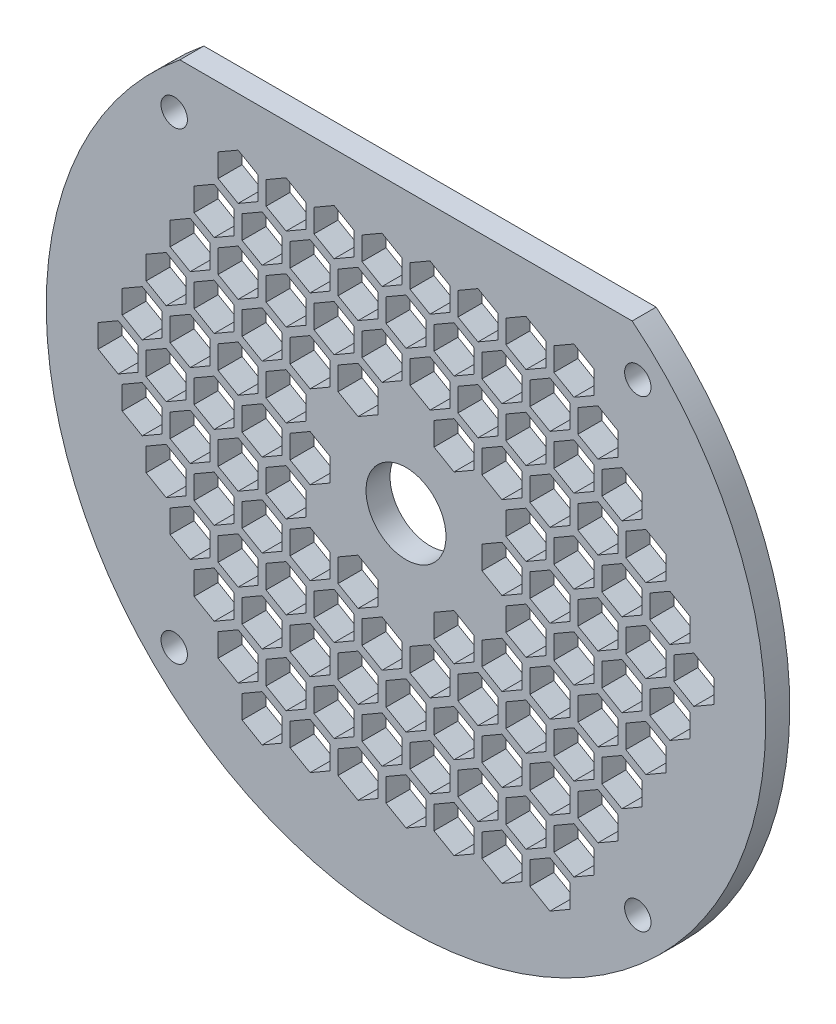
SolidWorks part; units mm, degrees
ref_plane "前视基准面" through (0, 0, 0) normal (0, 0, 1) x (1, 0, 0)
ref_plane "上视基准面" through (0, 0, 0) normal (0, 1, 0) x (1, 0, 0)
ref_plane "右视基准面" through (0, 0, 0) normal (1, 0, 0) x (0, 0, -1)
sketch "草图1" plane through (0, 0, 0) normal (0, 0, 1) x (1, 0, 0)
  circle A0 centre (0, 0) radius 90
extrude "凸台-拉伸1" add sketch "草图1" along normal blind 6
sketch "草图2" plane through (0, 0, 0) normal (0, 0, 1) x (1, 0, 0)
  line L0 (-200, 70) -> (200, 70)
  line L1 (200, 70) -> (200, 210)
  line L2 (200, 210) -> (-200, 210)
  line L3 (-200, 210) -> (-200, 70)
extrude "切除-拉伸1" cut sketch "草图2" along normal through all
sketch "草图5" plane through (0, 0, 0) normal (0, 0, 1) x (1, 0, 0)
  line L0 (24, 5.7735) -> (19, 2.8868)
  line L1 (19, 2.8868) -> (19, -2.8868)
  line L2 (19, -2.8868) -> (24, -5.7735)
  line L3 (24, -5.7735) -> (29, -2.8868)
  line L4 (29, -2.8868) -> (29, 2.8868)
  line L5 (29, 2.8868) -> (24, 5.7735)
  line L6 (-24, 5.7735) -> (-29, 2.8868)
  line L7 (-29, 2.8868) -> (-29, -2.8868)
  line L8 (-29, -2.8868) -> (-24, -5.7735)
  line L9 (-24, -5.7735) -> (-19, -2.8868)
  line L10 (-19, -2.8868) -> (-19, 2.8868)
  line L11 (-19, 2.8868) -> (-24, 5.7735)
  line L12 (36, 5.7735) -> (31, 2.8868)
  line L13 (31, 2.8868) -> (31, -2.8868)
  line L14 (31, -2.8868) -> (36, -5.7735)
  line L15 (36, -5.7735) -> (41, -2.8868)
  line L16 (41, -2.8868) -> (41, 2.8868)
  line L17 (41, 2.8868) -> (36, 5.7735)
  line L18 (-36, 5.7735) -> (-41, 2.8868)
  line L19 (-41, 2.8868) -> (-41, -2.8868)
  line L20 (-41, -2.8868) -> (-36, -5.7735)
  line L21 (-36, -5.7735) -> (-31, -2.8868)
  line L22 (-31, -2.8868) -> (-31, 2.8868)
  line L23 (-31, 2.8868) -> (-36, 5.7735)
  line L24 (48, 5.7735) -> (43, 2.8868)
  line L25 (43, 2.8868) -> (43, -2.8868)
  line L26 (43, -2.8868) -> (48, -5.7735)
  line L27 (48, -5.7735) -> (53, -2.8868)
  line L28 (53, -2.8868) -> (53, 2.8868)
  line L29 (53, 2.8868) -> (48, 5.7735)
  line L30 (-48, 5.7735) -> (-53, 2.8868)
  line L31 (-53, 2.8868) -> (-53, -2.8868)
  line L32 (-53, -2.8868) -> (-48, -5.7735)
  line L33 (-48, -5.7735) -> (-43, -2.8868)
  line L34 (-43, -2.8868) -> (-43, 2.8868)
  line L35 (-43, 2.8868) -> (-48, 5.7735)
  line L36 (60, 5.7735) -> (55, 2.8868)
  line L37 (55, 2.8868) -> (55, -2.8868)
  line L38 (55, -2.8868) -> (60, -5.7735)
  line L39 (60, -5.7735) -> (65, -2.8868)
  line L40 (65, -2.8868) -> (65, 2.8868)
  line L41 (65, 2.8868) -> (60, 5.7735)
  line L42 (-60, 5.7735) -> (-65, 2.8868)
  line L43 (-65, 2.8868) -> (-65, -2.8868)
  line L44 (-65, -2.8868) -> (-60, -5.7735)
  line L45 (-60, -5.7735) -> (-55, -2.8868)
  line L46 (-55, -2.8868) -> (-55, 2.8868)
  line L47 (-55, 2.8868) -> (-60, 5.7735)
  line L48 (72, 5.7735) -> (67, 2.8868)
  line L49 (67, 2.8868) -> (67, -2.8868)
  line L50 (67, -2.8868) -> (72, -5.7735)
  line L51 (72, -5.7735) -> (77, -2.8868)
  line L52 (77, -2.8868) -> (77, 2.8868)
  line L53 (77, 2.8868) -> (72, 5.7735)
  line L54 (-72, 5.7735) -> (-77, 2.8868)
  line L55 (-77, 2.8868) -> (-77, -2.8868)
  line L56 (-77, -2.8868) -> (-72, -5.7735)
  line L57 (-72, -5.7735) -> (-67, -2.8868)
  line L58 (-67, -2.8868) -> (-67, 2.8868)
  line L59 (-67, 2.8868) -> (-72, 5.7735)
  line L60 (30, 16.1655) -> (25, 13.2788)
  line L61 (25, 13.2788) -> (25, 7.5052)
  line L62 (25, 7.5052) -> (30, 4.6185)
  line L63 (30, 4.6185) -> (35, 7.5052)
  line L64 (35, 7.5052) -> (35, 13.2788)
  line L65 (35, 13.2788) -> (30, 16.1655)
  line L66 (-30, 16.1655) -> (-35, 13.2788)
  line L67 (-35, 13.2788) -> (-35, 7.5052)
  line L68 (-35, 7.5052) -> (-30, 4.6185)
  line L69 (-30, 4.6185) -> (-25, 7.5052)
  line L70 (-25, 7.5052) -> (-25, 13.2788)
  line L71 (-25, 13.2788) -> (-30, 16.1655)
  line L72 (42, 16.1655) -> (37, 13.2788)
  line L73 (37, 13.2788) -> (37, 7.5052)
  line L74 (37, 7.5052) -> (42, 4.6185)
  line L75 (42, 4.6185) -> (47, 7.5052)
  line L76 (47, 7.5052) -> (47, 13.2788)
  line L77 (47, 13.2788) -> (42, 16.1655)
  line L78 (-42, 16.1655) -> (-47, 13.2788)
  line L79 (-47, 13.2788) -> (-47, 7.5052)
  line L80 (-47, 7.5052) -> (-42, 4.6185)
  line L81 (-42, 4.6185) -> (-37, 7.5052)
  line L82 (-37, 7.5052) -> (-37, 13.2788)
  line L83 (-37, 13.2788) -> (-42, 16.1655)
  line L84 (54, 16.1655) -> (49, 13.2788)
  line L85 (49, 13.2788) -> (49, 7.5052)
  line L86 (49, 7.5052) -> (54, 4.6185)
  line L87 (54, 4.6185) -> (59, 7.5052)
  line L88 (59, 7.5052) -> (59, 13.2788)
  line L89 (59, 13.2788) -> (54, 16.1655)
  line L90 (-54, 16.1655) -> (-59, 13.2788)
  line L91 (-59, 13.2788) -> (-59, 7.5052)
  line L92 (-59, 7.5052) -> (-54, 4.6185)
  line L93 (-54, 4.6185) -> (-49, 7.5052)
  line L94 (-49, 7.5052) -> (-49, 13.2788)
  line L95 (-49, 13.2788) -> (-54, 16.1655)
  line L96 (66, 16.1655) -> (61, 13.2788)
  line L97 (61, 13.2788) -> (61, 7.5052)
  line L98 (61, 7.5052) -> (66, 4.6185)
  line L99 (66, 4.6185) -> (71, 7.5052)
  line L100 (71, 7.5052) -> (71, 13.2788)
  line L101 (71, 13.2788) -> (66, 16.1655)
  line L102 (-66, 16.1655) -> (-71, 13.2788)
  line L103 (-71, 13.2788) -> (-71, 7.5052)
  line L104 (-71, 7.5052) -> (-66, 4.6185)
  line L105 (-66, 4.6185) -> (-61, 7.5052)
  line L106 (-61, 7.5052) -> (-61, 13.2788)
  line L107 (-61, 13.2788) -> (-66, 16.1655)
  line L108 (30, -4.6185) -> (25, -7.5052)
  line L109 (25, -7.5052) -> (25, -13.2788)
  line L110 (25, -13.2788) -> (30, -16.1655)
  line L111 (30, -16.1655) -> (35, -13.2788)
  line L112 (35, -13.2788) -> (35, -7.5052)
  line L113 (35, -7.5052) -> (30, -4.6185)
  line L114 (-30, -4.6185) -> (-35, -7.5052)
  line L115 (-35, -7.5052) -> (-35, -13.2788)
  line L116 (-35, -13.2788) -> (-30, -16.1655)
  line L117 (-30, -16.1655) -> (-25, -13.2788)
  line L118 (-25, -13.2788) -> (-25, -7.5052)
  line L119 (-25, -7.5052) -> (-30, -4.6185)
  line L120 (42, -4.6185) -> (37, -7.5052)
  line L121 (37, -7.5052) -> (37, -13.2788)
  line L122 (37, -13.2788) -> (42, -16.1655)
  line L123 (42, -16.1655) -> (47, -13.2788)
  line L124 (47, -13.2788) -> (47, -7.5052)
  line L125 (47, -7.5052) -> (42, -4.6185)
  line L126 (-42, -4.6185) -> (-47, -7.5052)
  line L127 (-47, -7.5052) -> (-47, -13.2788)
  line L128 (-47, -13.2788) -> (-42, -16.1655)
  line L129 (-42, -16.1655) -> (-37, -13.2788)
  line L130 (-37, -13.2788) -> (-37, -7.5052)
  line L131 (-37, -7.5052) -> (-42, -4.6185)
  line L132 (54, -4.6185) -> (49, -7.5052)
  line L133 (49, -7.5052) -> (49, -13.2788)
  line L134 (49, -13.2788) -> (54, -16.1655)
  line L135 (54, -16.1655) -> (59, -13.2788)
  line L136 (59, -13.2788) -> (59, -7.5052)
  line L137 (59, -7.5052) -> (54, -4.6185)
  line L138 (-54, -4.6185) -> (-59, -7.5052)
  line L139 (-59, -7.5052) -> (-59, -13.2788)
  line L140 (-59, -13.2788) -> (-54, -16.1655)
  line L141 (-54, -16.1655) -> (-49, -13.2788)
  line L142 (-49, -13.2788) -> (-49, -7.5052)
  line L143 (-49, -7.5052) -> (-54, -4.6185)
  line L144 (66, -4.6185) -> (61, -7.5052)
  line L145 (61, -7.5052) -> (61, -13.2788)
  line L146 (61, -13.2788) -> (66, -16.1655)
  line L147 (66, -16.1655) -> (71, -13.2788)
  line L148 (71, -13.2788) -> (71, -7.5052)
  line L149 (71, -7.5052) -> (66, -4.6185)
  line L150 (-66, -4.6185) -> (-71, -7.5052)
  line L151 (-71, -7.5052) -> (-71, -13.2788)
  line L152 (-71, -13.2788) -> (-66, -16.1655)
  line L153 (-66, -16.1655) -> (-61, -13.2788)
  line L154 (-61, -13.2788) -> (-61, -7.5052)
  line L155 (-61, -7.5052) -> (-66, -4.6185)
extrude "切除-拉伸4" cut sketch "草图5" along normal through all
sketch "草图7" plane through (0, 0, 0) normal (0, 0, 1) x (1, 0, 0)
  line L0 (12, 26.5575) -> (7, 23.6708)
  line L1 (7, 23.6708) -> (7, 17.8972)
  line L2 (7, 17.8972) -> (12, 15.0105)
  line L3 (12, 15.0105) -> (17, 17.8972)
  line L4 (17, 17.8972) -> (17, 23.6708)
  line L5 (17, 23.6708) -> (12, 26.5575)
  line L6 (-12, 26.5575) -> (-17, 23.6708)
  line L7 (-17, 23.6708) -> (-17, 17.8972)
  line L8 (-17, 17.8972) -> (-12, 15.0105)
  line L9 (-12, 15.0105) -> (-7, 17.8972)
  line L10 (-7, 17.8972) -> (-7, 23.6708)
  line L11 (-7, 23.6708) -> (-12, 26.5575)
  line L12 (24, 26.5575) -> (19, 23.6708)
  line L13 (19, 23.6708) -> (19, 17.8972)
  line L14 (19, 17.8972) -> (24, 15.0105)
  line L15 (24, 15.0105) -> (29, 17.8972)
  line L16 (29, 17.8972) -> (29, 23.6708)
  line L17 (29, 23.6708) -> (24, 26.5575)
  line L18 (-24, 26.5575) -> (-29, 23.6708)
  line L19 (-29, 23.6708) -> (-29, 17.8972)
  line L20 (-29, 17.8972) -> (-24, 15.0105)
  line L21 (-24, 15.0105) -> (-19, 17.8972)
  line L22 (-19, 17.8972) -> (-19, 23.6708)
  line L23 (-19, 23.6708) -> (-24, 26.5575)
  line L24 (36, 26.5575) -> (31, 23.6708)
  line L25 (31, 23.6708) -> (31, 17.8972)
  line L26 (31, 17.8972) -> (36, 15.0105)
  line L27 (36, 15.0105) -> (41, 17.8972)
  line L28 (41, 17.8972) -> (41, 23.6708)
  line L29 (41, 23.6708) -> (36, 26.5575)
  line L30 (-36, 26.5575) -> (-41, 23.6708)
  line L31 (-41, 23.6708) -> (-41, 17.8972)
  line L32 (-41, 17.8972) -> (-36, 15.0105)
  line L33 (-36, 15.0105) -> (-31, 17.8972)
  line L34 (-31, 17.8972) -> (-31, 23.6708)
  line L35 (-31, 23.6708) -> (-36, 26.5575)
  line L36 (48, 26.5575) -> (43, 23.6708)
  line L37 (43, 23.6708) -> (43, 17.8972)
  line L38 (43, 17.8972) -> (48, 15.0105)
  line L39 (48, 15.0105) -> (53, 17.8972)
  line L40 (53, 17.8972) -> (53, 23.6708)
  line L41 (53, 23.6708) -> (48, 26.5575)
  line L42 (-48, 26.5575) -> (-53, 23.6708)
  line L43 (-53, 23.6708) -> (-53, 17.8972)
  line L44 (-53, 17.8972) -> (-48, 15.0105)
  line L45 (-48, 15.0105) -> (-43, 17.8972)
  line L46 (-43, 17.8972) -> (-43, 23.6708)
  line L47 (-43, 23.6708) -> (-48, 26.5575)
  line L48 (60, 26.5575) -> (55, 23.6708)
  line L49 (55, 23.6708) -> (55, 17.8972)
  line L50 (55, 17.8972) -> (60, 15.0105)
  line L51 (60, 15.0105) -> (65, 17.8972)
  line L52 (65, 17.8972) -> (65, 23.6708)
  line L53 (65, 23.6708) -> (60, 26.5575)
  line L54 (-60, 26.5575) -> (-65, 23.6708)
  line L55 (-65, 23.6708) -> (-65, 17.8972)
  line L56 (-65, 17.8972) -> (-60, 15.0105)
  line L57 (-60, 15.0105) -> (-55, 17.8972)
  line L58 (-55, 17.8972) -> (-55, 23.6708)
  line L59 (-55, 23.6708) -> (-60, 26.5575)
  line L60 (12, -15.0105) -> (7, -17.8972)
  line L61 (7, -17.8972) -> (7, -23.6708)
  line L62 (7, -23.6708) -> (12, -26.5575)
  line L63 (12, -26.5575) -> (17, -23.6708)
  line L64 (17, -23.6708) -> (17, -17.8972)
  line L65 (17, -17.8972) -> (12, -15.0105)
  line L66 (-12, -15.0105) -> (-17, -17.8972)
  line L67 (-17, -17.8972) -> (-17, -23.6708)
  line L68 (-17, -23.6708) -> (-12, -26.5575)
  line L69 (-12, -26.5575) -> (-7, -23.6708)
  line L70 (-7, -23.6708) -> (-7, -17.8972)
  line L71 (-7, -17.8972) -> (-12, -15.0105)
  line L72 (24, -15.0105) -> (19, -17.8972)
  line L73 (19, -17.8972) -> (19, -23.6708)
  line L74 (19, -23.6708) -> (24, -26.5575)
  line L75 (24, -26.5575) -> (29, -23.6708)
  line L76 (29, -23.6708) -> (29, -17.8972)
  line L77 (29, -17.8972) -> (24, -15.0105)
  line L78 (-24, -15.0105) -> (-29, -17.8972)
  line L79 (-29, -17.8972) -> (-29, -23.6708)
  line L80 (-29, -23.6708) -> (-24, -26.5575)
  line L81 (-24, -26.5575) -> (-19, -23.6708)
  line L82 (-19, -23.6708) -> (-19, -17.8972)
  line L83 (-19, -17.8972) -> (-24, -15.0105)
  line L84 (36, -15.0105) -> (31, -17.8972)
  line L85 (31, -17.8972) -> (31, -23.6708)
  line L86 (31, -23.6708) -> (36, -26.5575)
  line L87 (36, -26.5575) -> (41, -23.6708)
  line L88 (41, -23.6708) -> (41, -17.8972)
  line L89 (41, -17.8972) -> (36, -15.0105)
  line L90 (-36, -15.0105) -> (-41, -17.8972)
  line L91 (-41, -17.8972) -> (-41, -23.6708)
  line L92 (-41, -23.6708) -> (-36, -26.5575)
  line L93 (-36, -26.5575) -> (-31, -23.6708)
  line L94 (-31, -23.6708) -> (-31, -17.8972)
  line L95 (-31, -17.8972) -> (-36, -15.0105)
  line L96 (48, -15.0105) -> (43, -17.8972)
  line L97 (43, -17.8972) -> (43, -23.6708)
  line L98 (43, -23.6708) -> (48, -26.5575)
  line L99 (48, -26.5575) -> (53, -23.6708)
  line L100 (53, -23.6708) -> (53, -17.8972)
  line L101 (53, -17.8972) -> (48, -15.0105)
  line L102 (-48, -15.0105) -> (-53, -17.8972)
  line L103 (-53, -17.8972) -> (-53, -23.6708)
  line L104 (-53, -23.6708) -> (-48, -26.5575)
  line L105 (-48, -26.5575) -> (-43, -23.6708)
  line L106 (-43, -23.6708) -> (-43, -17.8972)
  line L107 (-43, -17.8972) -> (-48, -15.0105)
  line L108 (60, -15.0105) -> (55, -17.8972)
  line L109 (55, -17.8972) -> (55, -23.6708)
  line L110 (55, -23.6708) -> (60, -26.5575)
  line L111 (60, -26.5575) -> (65, -23.6708)
  line L112 (65, -23.6708) -> (65, -17.8972)
  line L113 (65, -17.8972) -> (60, -15.0105)
  line L114 (-60, -15.0105) -> (-65, -17.8972)
  line L115 (-65, -17.8972) -> (-65, -23.6708)
  line L116 (-65, -23.6708) -> (-60, -26.5575)
  line L117 (-60, -26.5575) -> (-55, -23.6708)
  line L118 (-55, -23.6708) -> (-55, -17.8972)
  line L119 (-55, -17.8972) -> (-60, -15.0105)
  line L120 (6, 36.9495) -> (1, 34.0628)
  line L121 (1, 34.0628) -> (1, 28.2892)
  line L122 (1, 28.2892) -> (6, 25.4025)
  line L123 (6, 25.4025) -> (11, 28.2892)
  line L124 (11, 28.2892) -> (11, 34.0628)
  line L125 (11, 34.0628) -> (6, 36.9495)
  line L126 (-6, 36.9495) -> (-11, 34.0628)
  line L127 (-11, 34.0628) -> (-11, 28.2892)
  line L128 (-11, 28.2892) -> (-6, 25.4025)
  line L129 (-6, 25.4025) -> (-1, 28.2892)
  line L130 (-1, 28.2892) -> (-1, 34.0628)
  line L131 (-1, 34.0628) -> (-6, 36.9495)
  line L132 (18, 36.9495) -> (13, 34.0628)
  line L133 (13, 34.0628) -> (13, 28.2892)
  line L134 (13, 28.2892) -> (18, 25.4025)
  line L135 (18, 25.4025) -> (23, 28.2892)
  line L136 (23, 28.2892) -> (23, 34.0628)
  line L137 (23, 34.0628) -> (18, 36.9495)
  line L138 (-18, 36.9495) -> (-23, 34.0628)
  line L139 (-23, 34.0628) -> (-23, 28.2892)
  line L140 (-23, 28.2892) -> (-18, 25.4025)
  line L141 (-18, 25.4025) -> (-13, 28.2892)
  line L142 (-13, 28.2892) -> (-13, 34.0628)
  line L143 (-13, 34.0628) -> (-18, 36.9495)
  line L144 (30, 36.9495) -> (25, 34.0628)
  line L145 (25, 34.0628) -> (25, 28.2892)
  line L146 (25, 28.2892) -> (30, 25.4025)
  line L147 (30, 25.4025) -> (35, 28.2892)
  line L148 (35, 28.2892) -> (35, 34.0628)
  line L149 (35, 34.0628) -> (30, 36.9495)
  line L150 (-30, 36.9495) -> (-35, 34.0628)
  line L151 (-35, 34.0628) -> (-35, 28.2892)
  line L152 (-35, 28.2892) -> (-30, 25.4025)
  line L153 (-30, 25.4025) -> (-25, 28.2892)
  line L154 (-25, 28.2892) -> (-25, 34.0628)
  line L155 (-25, 34.0628) -> (-30, 36.9495)
  line L156 (42, 36.9495) -> (37, 34.0628)
  line L157 (37, 34.0628) -> (37, 28.2892)
  line L158 (37, 28.2892) -> (42, 25.4025)
  line L159 (42, 25.4025) -> (47, 28.2892)
  line L160 (47, 28.2892) -> (47, 34.0628)
  line L161 (47, 34.0628) -> (42, 36.9495)
  line L162 (-42, 36.9495) -> (-47, 34.0628)
  line L163 (-47, 34.0628) -> (-47, 28.2892)
  line L164 (-47, 28.2892) -> (-42, 25.4025)
  line L165 (-42, 25.4025) -> (-37, 28.2892)
  line L166 (-37, 28.2892) -> (-37, 34.0628)
  line L167 (-37, 34.0628) -> (-42, 36.9495)
  line L168 (54, 36.9495) -> (49, 34.0628)
  line L169 (49, 34.0628) -> (49, 28.2892)
  line L170 (49, 28.2892) -> (54, 25.4025)
  line L171 (54, 25.4025) -> (59, 28.2892)
  line L172 (59, 28.2892) -> (59, 34.0628)
  line L173 (59, 34.0628) -> (54, 36.9495)
  line L174 (-54, 36.9495) -> (-59, 34.0628)
  line L175 (-59, 34.0628) -> (-59, 28.2892)
  line L176 (-59, 28.2892) -> (-54, 25.4025)
  line L177 (-54, 25.4025) -> (-49, 28.2892)
  line L178 (-49, 28.2892) -> (-49, 34.0628)
  line L179 (-49, 34.0628) -> (-54, 36.9495)
  line L180 (6, -25.4025) -> (1, -28.2892)
  line L181 (1, -28.2892) -> (1, -34.0628)
  line L182 (1, -34.0628) -> (6, -36.9495)
  line L183 (6, -36.9495) -> (11, -34.0628)
  line L184 (11, -34.0628) -> (11, -28.2892)
  line L185 (11, -28.2892) -> (6, -25.4025)
  line L186 (-6, -25.4025) -> (-11, -28.2892)
  line L187 (-11, -28.2892) -> (-11, -34.0628)
  line L188 (-11, -34.0628) -> (-6, -36.9495)
  line L189 (-6, -36.9495) -> (-1, -34.0628)
  line L190 (-1, -34.0628) -> (-1, -28.2892)
  line L191 (-1, -28.2892) -> (-6, -25.4025)
  line L192 (18, -25.4025) -> (13, -28.2892)
  line L193 (13, -28.2892) -> (13, -34.0628)
  line L194 (13, -34.0628) -> (18, -36.9495)
  line L195 (18, -36.9495) -> (23, -34.0628)
  line L196 (23, -34.0628) -> (23, -28.2892)
  line L197 (23, -28.2892) -> (18, -25.4025)
  line L198 (-18, -25.4025) -> (-23, -28.2892)
  line L199 (-23, -28.2892) -> (-23, -34.0628)
  line L200 (-23, -34.0628) -> (-18, -36.9495)
  line L201 (-18, -36.9495) -> (-13, -34.0628)
  line L202 (-13, -34.0628) -> (-13, -28.2892)
  line L203 (-13, -28.2892) -> (-18, -25.4025)
  line L204 (30, -25.4025) -> (25, -28.2892)
  line L205 (25, -28.2892) -> (25, -34.0628)
  line L206 (25, -34.0628) -> (30, -36.9495)
  line L207 (30, -36.9495) -> (35, -34.0628)
  line L208 (35, -34.0628) -> (35, -28.2892)
  line L209 (35, -28.2892) -> (30, -25.4025)
  line L210 (-30, -25.4025) -> (-35, -28.2892)
  line L211 (-35, -28.2892) -> (-35, -34.0628)
  line L212 (-35, -34.0628) -> (-30, -36.9495)
  line L213 (-30, -36.9495) -> (-25, -34.0628)
  line L214 (-25, -34.0628) -> (-25, -28.2892)
  line L215 (-25, -28.2892) -> (-30, -25.4025)
  line L216 (42, -25.4025) -> (37, -28.2892)
  line L217 (37, -28.2892) -> (37, -34.0628)
  line L218 (37, -34.0628) -> (42, -36.9495)
  line L219 (42, -36.9495) -> (47, -34.0628)
  line L220 (47, -34.0628) -> (47, -28.2892)
  line L221 (47, -28.2892) -> (42, -25.4025)
  line L222 (-42, -25.4025) -> (-47, -28.2892)
  line L223 (-47, -28.2892) -> (-47, -34.0628)
  line L224 (-47, -34.0628) -> (-42, -36.9495)
  line L225 (-42, -36.9495) -> (-37, -34.0628)
  line L226 (-37, -34.0628) -> (-37, -28.2892)
  line L227 (-37, -28.2892) -> (-42, -25.4025)
  line L228 (54, -25.4025) -> (49, -28.2892)
  line L229 (49, -28.2892) -> (49, -34.0628)
  line L230 (49, -34.0628) -> (54, -36.9495)
  line L231 (54, -36.9495) -> (59, -34.0628)
  line L232 (59, -34.0628) -> (59, -28.2892)
  line L233 (59, -28.2892) -> (54, -25.4025)
  line L234 (-54, -25.4025) -> (-59, -28.2892)
  line L235 (-59, -28.2892) -> (-59, -34.0628)
  line L236 (-59, -34.0628) -> (-54, -36.9495)
  line L237 (-54, -36.9495) -> (-49, -34.0628)
  line L238 (-49, -34.0628) -> (-49, -28.2892)
  line L239 (-49, -28.2892) -> (-54, -25.4025)
  line L240 (0, 47.3415) -> (-5, 44.4548)
  line L241 (-5, 44.4548) -> (-5, 38.6812)
  line L242 (-5, 38.6812) -> (0, 35.7945)
  line L243 (0, 35.7945) -> (5, 38.6812)
  line L244 (5, 38.6812) -> (5, 44.4548)
  line L245 (5, 44.4548) -> (0, 47.3415)
  line L246 (12, 47.3415) -> (7, 44.4548)
  line L247 (7, 44.4548) -> (7, 38.6812)
  line L248 (7, 38.6812) -> (12, 35.7945)
  line L249 (12, 35.7945) -> (17, 38.6812)
  line L250 (17, 38.6812) -> (17, 44.4548)
  line L251 (17, 44.4548) -> (12, 47.3415)
  line L252 (-12, 47.3415) -> (-17, 44.4548)
  line L253 (-17, 44.4548) -> (-17, 38.6812)
  line L254 (-17, 38.6812) -> (-12, 35.7945)
  line L255 (-12, 35.7945) -> (-7, 38.6812)
  line L256 (-7, 38.6812) -> (-7, 44.4548)
  line L257 (-7, 44.4548) -> (-12, 47.3415)
  line L258 (24, 47.3415) -> (19, 44.4548)
  line L259 (19, 44.4548) -> (19, 38.6812)
  line L260 (19, 38.6812) -> (24, 35.7945)
  line L261 (24, 35.7945) -> (29, 38.6812)
  line L262 (29, 38.6812) -> (29, 44.4548)
  line L263 (29, 44.4548) -> (24, 47.3415)
  line L264 (-24, 47.3415) -> (-29, 44.4548)
  line L265 (-29, 44.4548) -> (-29, 38.6812)
  line L266 (-29, 38.6812) -> (-24, 35.7945)
  line L267 (-24, 35.7945) -> (-19, 38.6812)
  line L268 (-19, 38.6812) -> (-19, 44.4548)
  line L269 (-19, 44.4548) -> (-24, 47.3415)
  line L270 (36, 47.3415) -> (31, 44.4548)
  line L271 (31, 44.4548) -> (31, 38.6812)
  line L272 (31, 38.6812) -> (36, 35.7945)
  line L273 (36, 35.7945) -> (41, 38.6812)
  line L274 (41, 38.6812) -> (41, 44.4548)
  line L275 (41, 44.4548) -> (36, 47.3415)
  line L276 (-36, 47.3415) -> (-41, 44.4548)
  line L277 (-41, 44.4548) -> (-41, 38.6812)
  line L278 (-41, 38.6812) -> (-36, 35.7945)
  line L279 (-36, 35.7945) -> (-31, 38.6812)
  line L280 (-31, 38.6812) -> (-31, 44.4548)
  line L281 (-31, 44.4548) -> (-36, 47.3415)
  line L282 (48, 47.3415) -> (43, 44.4548)
  line L283 (43, 44.4548) -> (43, 38.6812)
  line L284 (43, 38.6812) -> (48, 35.7945)
  line L285 (48, 35.7945) -> (53, 38.6812)
  line L286 (53, 38.6812) -> (53, 44.4548)
  line L287 (53, 44.4548) -> (48, 47.3415)
  line L288 (-48, 47.3415) -> (-53, 44.4548)
  line L289 (-53, 44.4548) -> (-53, 38.6812)
  line L290 (-53, 38.6812) -> (-48, 35.7945)
  line L291 (-48, 35.7945) -> (-43, 38.6812)
  line L292 (-43, 38.6812) -> (-43, 44.4548)
  line L293 (-43, 44.4548) -> (-48, 47.3415)
  line L294 (0, -35.7945) -> (-5, -38.6812)
  line L295 (-5, -38.6812) -> (-5, -44.4548)
  line L296 (-5, -44.4548) -> (0, -47.3415)
  line L297 (0, -47.3415) -> (5, -44.4548)
  line L298 (5, -44.4548) -> (5, -38.6812)
  line L299 (5, -38.6812) -> (0, -35.7945)
  line L300 (12, -35.7945) -> (7, -38.6812)
  line L301 (7, -38.6812) -> (7, -44.4548)
  line L302 (7, -44.4548) -> (12, -47.3415)
  line L303 (12, -47.3415) -> (17, -44.4548)
  line L304 (17, -44.4548) -> (17, -38.6812)
  line L305 (17, -38.6812) -> (12, -35.7945)
  line L306 (-12, -35.7945) -> (-17, -38.6812)
  line L307 (-17, -38.6812) -> (-17, -44.4548)
  line L308 (-17, -44.4548) -> (-12, -47.3415)
  line L309 (-12, -47.3415) -> (-7, -44.4548)
  line L310 (-7, -44.4548) -> (-7, -38.6812)
  line L311 (-7, -38.6812) -> (-12, -35.7945)
  line L312 (24, -35.7945) -> (19, -38.6812)
  line L313 (19, -38.6812) -> (19, -44.4548)
  line L314 (19, -44.4548) -> (24, -47.3415)
  line L315 (24, -47.3415) -> (29, -44.4548)
  line L316 (29, -44.4548) -> (29, -38.6812)
  line L317 (29, -38.6812) -> (24, -35.7945)
  line L318 (-24, -35.7945) -> (-29, -38.6812)
  line L319 (-29, -38.6812) -> (-29, -44.4548)
  line L320 (-29, -44.4548) -> (-24, -47.3415)
  line L321 (-24, -47.3415) -> (-19, -44.4548)
  line L322 (-19, -44.4548) -> (-19, -38.6812)
  line L323 (-19, -38.6812) -> (-24, -35.7945)
  line L324 (36, -35.7945) -> (31, -38.6812)
  line L325 (31, -38.6812) -> (31, -44.4548)
  line L326 (31, -44.4548) -> (36, -47.3415)
  line L327 (36, -47.3415) -> (41, -44.4548)
  line L328 (41, -44.4548) -> (41, -38.6812)
  line L329 (41, -38.6812) -> (36, -35.7945)
  line L330 (-36, -35.7945) -> (-41, -38.6812)
  line L331 (-41, -38.6812) -> (-41, -44.4548)
  line L332 (-41, -44.4548) -> (-36, -47.3415)
  line L333 (-36, -47.3415) -> (-31, -44.4548)
  line L334 (-31, -44.4548) -> (-31, -38.6812)
  line L335 (-31, -38.6812) -> (-36, -35.7945)
  line L336 (48, -35.7945) -> (43, -38.6812)
  line L337 (43, -38.6812) -> (43, -44.4548)
  line L338 (43, -44.4548) -> (48, -47.3415)
  line L339 (48, -47.3415) -> (53, -44.4548)
  line L340 (53, -44.4548) -> (53, -38.6812)
  line L341 (53, -38.6812) -> (48, -35.7945)
  line L342 (-48, -35.7945) -> (-53, -38.6812)
  line L343 (-53, -38.6812) -> (-53, -44.4548)
  line L344 (-53, -44.4548) -> (-48, -47.3415)
  line L345 (-48, -47.3415) -> (-43, -44.4548)
  line L346 (-43, -44.4548) -> (-43, -38.6812)
  line L347 (-43, -38.6812) -> (-48, -35.7945)
extrude "切除-拉伸6" cut sketch "草图7" along normal through all
sketch "草图9" plane through (0, 0, 0) normal (0, 0, 1) x (1, 0, 0)
  line L0 (6, 57.7335) -> (1, 54.8468)
  line L1 (1, 54.8468) -> (1, 49.0732)
  line L2 (1, 49.0732) -> (6, 46.1865)
  line L3 (6, 46.1865) -> (11, 49.0732)
  line L4 (11, 49.0732) -> (11, 54.8468)
  line L5 (11, 54.8468) -> (6, 57.7335)
  line L6 (-6, 57.7335) -> (-11, 54.8468)
  line L7 (-11, 54.8468) -> (-11, 49.0732)
  line L8 (-11, 49.0732) -> (-6, 46.1865)
  line L9 (-6, 46.1865) -> (-1, 49.0732)
  line L10 (-1, 49.0732) -> (-1, 54.8468)
  line L11 (-1, 54.8468) -> (-6, 57.7335)
  line L12 (18, 57.7335) -> (13, 54.8468)
  line L13 (13, 54.8468) -> (13, 49.0732)
  line L14 (13, 49.0732) -> (18, 46.1865)
  line L15 (18, 46.1865) -> (23, 49.0732)
  line L16 (23, 49.0732) -> (23, 54.8468)
  line L17 (23, 54.8468) -> (18, 57.7335)
  line L18 (-18, 57.7335) -> (-23, 54.8468)
  line L19 (-23, 54.8468) -> (-23, 49.0732)
  line L20 (-23, 49.0732) -> (-18, 46.1865)
  line L21 (-18, 46.1865) -> (-13, 49.0732)
  line L22 (-13, 49.0732) -> (-13, 54.8468)
  line L23 (-13, 54.8468) -> (-18, 57.7335)
  line L24 (30, 57.7335) -> (25, 54.8468)
  line L25 (25, 54.8468) -> (25, 49.0732)
  line L26 (25, 49.0732) -> (30, 46.1865)
  line L27 (30, 46.1865) -> (35, 49.0732)
  line L28 (35, 49.0732) -> (35, 54.8468)
  line L29 (35, 54.8468) -> (30, 57.7335)
  line L30 (-30, 57.7335) -> (-35, 54.8468)
  line L31 (-35, 54.8468) -> (-35, 49.0732)
  line L32 (-35, 49.0732) -> (-30, 46.1865)
  line L33 (-30, 46.1865) -> (-25, 49.0732)
  line L34 (-25, 49.0732) -> (-25, 54.8468)
  line L35 (-25, 54.8468) -> (-30, 57.7335)
  line L36 (42, 57.7335) -> (37, 54.8468)
  line L37 (37, 54.8468) -> (37, 49.0732)
  line L38 (37, 49.0732) -> (42, 46.1865)
  line L39 (42, 46.1865) -> (47, 49.0732)
  line L40 (47, 49.0732) -> (47, 54.8468)
  line L41 (47, 54.8468) -> (42, 57.7335)
  line L42 (-42, 57.7335) -> (-47, 54.8468)
  line L43 (-47, 54.8468) -> (-47, 49.0732)
  line L44 (-47, 49.0732) -> (-42, 46.1865)
  line L45 (-42, 46.1865) -> (-37, 49.0732)
  line L46 (-37, 49.0732) -> (-37, 54.8468)
  line L47 (-37, 54.8468) -> (-42, 57.7335)
  line L48 (6, -46.1865) -> (1, -49.0732)
  line L49 (1, -49.0732) -> (1, -54.8468)
  line L50 (1, -54.8468) -> (6, -57.7335)
  line L51 (6, -57.7335) -> (11, -54.8468)
  line L52 (11, -54.8468) -> (11, -49.0732)
  line L53 (11, -49.0732) -> (6, -46.1865)
  line L54 (-6, -46.1865) -> (-11, -49.0732)
  line L55 (-11, -49.0732) -> (-11, -54.8468)
  line L56 (-11, -54.8468) -> (-6, -57.7335)
  line L57 (-6, -57.7335) -> (-1, -54.8468)
  line L58 (-1, -54.8468) -> (-1, -49.0732)
  line L59 (-1, -49.0732) -> (-6, -46.1865)
  line L60 (18, -46.1865) -> (13, -49.0732)
  line L61 (13, -49.0732) -> (13, -54.8468)
  line L62 (13, -54.8468) -> (18, -57.7335)
  line L63 (18, -57.7335) -> (23, -54.8468)
  line L64 (23, -54.8468) -> (23, -49.0732)
  line L65 (23, -49.0732) -> (18, -46.1865)
  line L66 (-18, -46.1865) -> (-23, -49.0732)
  line L67 (-23, -49.0732) -> (-23, -54.8468)
  line L68 (-23, -54.8468) -> (-18, -57.7335)
  line L69 (-18, -57.7335) -> (-13, -54.8468)
  line L70 (-13, -54.8468) -> (-13, -49.0732)
  line L71 (-13, -49.0732) -> (-18, -46.1865)
  line L72 (30, -46.1865) -> (25, -49.0732)
  line L73 (25, -49.0732) -> (25, -54.8468)
  line L74 (25, -54.8468) -> (30, -57.7335)
  line L75 (30, -57.7335) -> (35, -54.8468)
  line L76 (35, -54.8468) -> (35, -49.0732)
  line L77 (35, -49.0732) -> (30, -46.1865)
  line L78 (-30, -46.1865) -> (-35, -49.0732)
  line L79 (-35, -49.0732) -> (-35, -54.8468)
  line L80 (-35, -54.8468) -> (-30, -57.7335)
  line L81 (-30, -57.7335) -> (-25, -54.8468)
  line L82 (-25, -54.8468) -> (-25, -49.0732)
  line L83 (-25, -49.0732) -> (-30, -46.1865)
  line L84 (42, -46.1865) -> (37, -49.0732)
  line L85 (37, -49.0732) -> (37, -54.8468)
  line L86 (37, -54.8468) -> (42, -57.7335)
  line L87 (42, -57.7335) -> (47, -54.8468)
  line L88 (47, -54.8468) -> (47, -49.0732)
  line L89 (47, -49.0732) -> (42, -46.1865)
  line L90 (-42, -46.1865) -> (-47, -49.0732)
  line L91 (-47, -49.0732) -> (-47, -54.8468)
  line L92 (-47, -54.8468) -> (-42, -57.7335)
  line L93 (-42, -57.7335) -> (-37, -54.8468)
  line L94 (-37, -54.8468) -> (-37, -49.0732)
  line L95 (-37, -49.0732) -> (-42, -46.1865)
  line L96 (0, -56.5785) -> (-5, -59.4652)
  line L97 (-5, -59.4652) -> (-5, -65.2388)
  line L98 (-5, -65.2388) -> (0, -68.1255)
  line L99 (0, -68.1255) -> (5, -65.2388)
  line L100 (5, -65.2388) -> (5, -59.4652)
  line L101 (5, -59.4652) -> (0, -56.5785)
  line L102 (12, -56.5785) -> (7, -59.4652)
  line L103 (7, -59.4652) -> (7, -65.2388)
  line L104 (7, -65.2388) -> (12, -68.1255)
  line L105 (12, -68.1255) -> (17, -65.2388)
  line L106 (17, -65.2388) -> (17, -59.4652)
  line L107 (17, -59.4652) -> (12, -56.5785)
  line L108 (-12, -56.5785) -> (-17, -59.4652)
  line L109 (-17, -59.4652) -> (-17, -65.2388)
  line L110 (-17, -65.2388) -> (-12, -68.1255)
  line L111 (-12, -68.1255) -> (-7, -65.2388)
  line L112 (-7, -65.2388) -> (-7, -59.4652)
  line L113 (-7, -59.4652) -> (-12, -56.5785)
  line L114 (24, -56.5785) -> (19, -59.4652)
  line L115 (19, -59.4652) -> (19, -65.2388)
  line L116 (19, -65.2388) -> (24, -68.1255)
  line L117 (24, -68.1255) -> (29, -65.2388)
  line L118 (29, -65.2388) -> (29, -59.4652)
  line L119 (29, -59.4652) -> (24, -56.5785)
  line L120 (-24, -56.5785) -> (-29, -59.4652)
  line L121 (-29, -59.4652) -> (-29, -65.2388)
  line L122 (-29, -65.2388) -> (-24, -68.1255)
  line L123 (-24, -68.1255) -> (-19, -65.2388)
  line L124 (-19, -65.2388) -> (-19, -59.4652)
  line L125 (-19, -59.4652) -> (-24, -56.5785)
  line L126 (36, -56.5785) -> (31, -59.4652)
  line L127 (31, -59.4652) -> (31, -65.2388)
  line L128 (31, -65.2388) -> (36, -68.1255)
  line L129 (36, -68.1255) -> (41, -65.2388)
  line L130 (41, -65.2388) -> (41, -59.4652)
  line L131 (41, -59.4652) -> (36, -56.5785)
  line L132 (-36, -56.5785) -> (-41, -59.4652)
  line L133 (-41, -59.4652) -> (-41, -65.2388)
  line L134 (-41, -65.2388) -> (-36, -68.1255)
  line L135 (-36, -68.1255) -> (-31, -65.2388)
  line L136 (-31, -65.2388) -> (-31, -59.4652)
  line L137 (-31, -59.4652) -> (-36, -56.5785)
extrude "切除-拉伸8" cut sketch "草图9" along normal through all
sketch "草图10" plane through (0, 0, 0) normal (0, 0, 1) x (1, 0, 0)
  circle A0 centre (0, 0) radius 10
extrude "切除-拉伸9" cut sketch "草图10" along normal through all
sketch "草图11" plane through (0, 0, 0) normal (0, 0, 1) x (1, 0, 0)
  circle A0 centre (57.983, 57.983) radius 3.3
  circle A1 centre (-57.983, 57.983) radius 3.3
  circle A2 centre (-57.983, -57.983) radius 3.3
  circle A3 centre (57.983, -57.983) radius 3.3
extrude "切除-拉伸10" cut sketch "草图11" along normal through all
